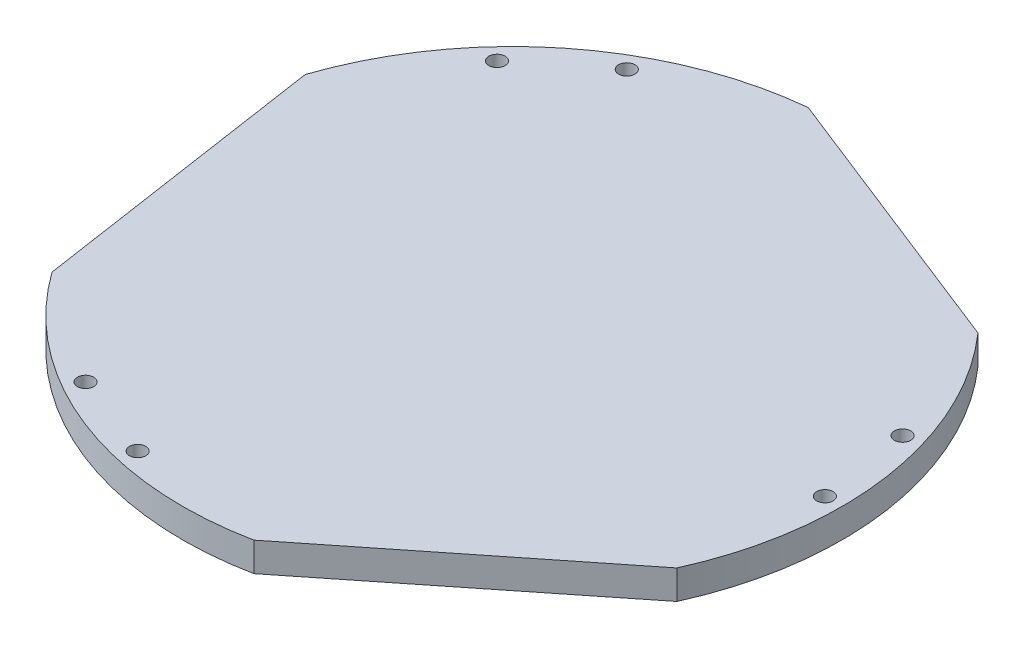
SolidWorks part; units mm, degrees
material "Oak"
ref_plane "Front Plane" through (0, 0, 0) normal (0, 0, 1) x (1, 0, 0)
ref_plane "Top Plane" through (0, 0, 0) normal (0, 1, 0) x (1, 0, 0)
ref_plane "Right Plane" through (0, 0, 0) normal (1, 0, 0) x (0, 0, -1)
sketch "Sketch1" plane through (0, 0, 0) normal (0, 0, 1) x (1, 0, 0)
  line L0 (0, -200000) -> (0, 218797.9879) construction
  line L1 (144.145, -24.4122) -> (144.145, -37.1122) construction
  line L2 (0, -24.4122) -> (144.145, -24.4122) construction
  line L3 (144.145, -37.1122) -> (0, -37.1122) construction
  line L4 (0, -200000) -> (0, 218797.9879) construction
  line L5 (144.145, -24.4122) -> (144.145, -37.1122)
  line L6 (0, -24.4122) -> (144.145, -24.4122)
  line L7 (144.145, -37.1122) -> (0, -37.1122)
  line L8 (0, -24.4122) -> (0, -37.1122)
revolve "Revolve1" add sketch "Sketch1" angle 360 about L4
hole_wizard "9/32 (0.28125) Diameter Hole1" positions "Sketch2" profile "Sketch3" hole size "9/32" standard "ANSI Inch" end condition up to next
sketch "Sketch2" plane through (0, -24.4122, 0) normal (0, 1, 0) x (1, 0, 0)
  line L0 (0, 0) -> (136.525, 0) construction
  line L3 (0, 0) -> (-68.2625, -118.2341) construction
  line L6 (0, 0) -> (-68.2625, 118.2341) construction
  line L7 (-99.8481, 93.1098) -> (0, 0) construction
  line L9 (0, 0) -> (-30.7114, -133.0259) construction
  line L12 (0, 0) -> (130.5595, 39.916) construction
  circle A0 centre (0, 0) radius 136.525
  point P0 (136.525, 0)
  point P2 (-68.2625, -118.2341)
  point P4 (-68.2625, 118.2341)
  point P32 (-99.8481, 93.1098)
  point P57 (130.5595, 39.916)
  point P60 (-30.7114, -133.0259)
  dimension "D3" = 17
  dimension "D1" = 120
  dimension "D2" = 120
  dimension "D4" = 120
  dimension "D5" = 120
sketch "Sketch3" plane through (136.525, -24.4122, 0) normal (1, 0, 0) x (0, 0, 1)
  line L0 (0, 0) -> (0, 12.7)
  line L1 (0, 12.7) -> (3.5719, 12.7)
  line L2 (3.5719, 12.7) -> (3.5719, 0)
  line L5 (3.5719, 0) -> (0, 0)
  line L11 (0, -6.35) -> (0, 107.95) construction
  dimension "Thru Hole Dia." = 7.1437
  dimension "Thru Hole Depth" = 12.7
sketch "Sketch4" plane through (0, -24.4122, 0) normal (0, 1, 0) x (1, 0, 0)
  line L0 (253.7221, 37.919) -> (-94.0222, -238.6893)
  line L1 (-94.0222, -238.6893) -> (-159.6999, 200.7703)
  line L2 (-159.6999, 200.7703) -> (253.7221, 37.919)
  line L3 (253.7221, 37.919) -> (0, 0) construction
  line L4 (130.5595, 39.916) -> (136.525, 0) construction
  circle A0 centre (0, 0) radius 128.27 construction
  point P6 (133.5423, 19.958)
  dimension "D1" = 256.54
extrude "Cut-Extrude1" cut sketch "Sketch4" against normal through all flip side to cut
